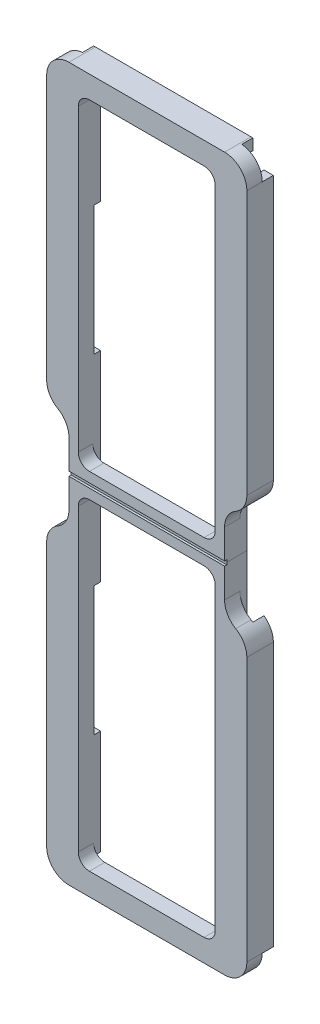
SolidWorks part; units mm, degrees
ref_plane "Front Plane" through (0, 0, 0) normal (1, 0, 0) x (0, 1, 0)
ref_plane "Top Plane" through (0, 0, 0) normal (0, 0, 1) x (0, 1, 0)
ref_plane "Right Plane" through (0, 0, 0) normal (0, 1, 0) x (-1, 0, 0)
sketch "Sketch1" plane through (0, 0, 0) normal (0, 0, 1) x (0, 1, 0)
  line L0 (279.1891, 2.675) -> (279.1891, 6.875) construction
  line L1 (-20.8109, 6.875) -> (279.1891, 6.875)
  line L2 (-20.8109, 6.875) -> (-20.8109, 2.675)
  line L3 (-20.8109, 2.675) -> (279.1891, 2.675)
  line L4 (279.1891, 6.875) -> (279.1891, 2.675)
  line L7 (129.1891, 2.675) -> (-20.8109, 2.675) construction
  line L8 (129.1891, 6.875) -> (-20.8109, 6.875) construction
  line L11 (26.1891, 2.675) -> (84.1891, 2.675)
  line L12 (26.1891, 2.675) -> (26.1891, 6.875)
  line L13 (26.1891, 6.875) -> (84.1891, 6.875)
  line L14 (84.1891, 2.675) -> (84.1891, 6.875)
  line L15 (174.1891, 2.675) -> (232.1891, 2.675)
  line L16 (174.1891, 2.675) -> (174.1891, 6.875)
  line L17 (174.1891, 6.875) -> (232.1891, 6.875)
  line L18 (232.1891, 2.675) -> (232.1891, 6.875)
  circle A0 centre (182.1891, 4.875) radius 1.65 construction
  circle A1 centre (224.1891, 4.875) radius 1.65 construction
  circle A2 centre (76.1891, 4.875) radius 1.65 construction
  circle A3 centre (34.1891, 4.875) radius 1.65 construction
  dimension "D1" = 0
  dimension "D2" = 0
  dimension "D3" = 0
  dimension "D4" = 8
  dimension "D5" = 8
  dimension "D6" = 8
  dimension "D7" = 8
extrude "Boss-Extrude1" add sketch "Sketch1" along normal blind 5 contours L2 L1 L4 L3
sketch "Sketch3" plane through (0, 0, 5) normal (0, 0, 1) x (1, 0, 0)
  line L4 (-2.675, 26.1891) -> (-2.675, 84.1891)
  line L5 (-2.675, 84.1891) -> (-6.875, 84.1891)
  line L6 (-6.875, 84.1891) -> (-6.875, 26.1891)
  line L7 (-6.875, 26.1891) -> (-2.675, 26.1891)
  line L8 (-2.675, 26.1891) -> (-2.675, 84.1891)
  line L9 (-2.675, 84.1891) -> (-6.875, 84.1891)
  line L10 (-6.875, 84.1891) -> (-6.875, 26.1891)
  line L11 (-6.875, 26.1891) -> (-2.675, 26.1891)
  line L12 (-6.875, 279.1891) -> (-6.875, -20.8109)
  line L13 (-2.675, 279.1891) -> (-6.875, 279.1891)
  line L14 (-2.675, -20.8109) -> (-2.675, 279.1891)
  line L15 (-6.875, -20.8109) -> (-2.675, -20.8109)
  line L16 (-6.875, 279.1891) -> (-6.875, -20.8109)
  line L17 (-2.675, 279.1891) -> (-6.875, 279.1891)
  line L18 (-2.675, -20.8109) -> (-2.675, 279.1891)
  line L19 (-6.875, -20.8109) -> (-2.675, -20.8109)
  line L20 (-2.675, 174.1891) -> (-2.675, 232.1891)
  line L21 (-6.875, 174.1891) -> (-2.675, 174.1891)
  line L22 (-6.875, 232.1891) -> (-6.875, 174.1891)
  line L23 (-2.675, 232.1891) -> (-6.875, 232.1891)
  line L24 (-2.675, 174.1891) -> (-2.675, 232.1891)
  line L25 (-6.875, 174.1891) -> (-2.675, 174.1891)
  line L26 (-6.875, 232.1891) -> (-6.875, 174.1891)
  line L27 (-2.675, 232.1891) -> (-6.875, 232.1891)
  dimension "D1" = 0
  dimension "D2" = 0
  dimension "D3" = 0
extrude "Cut-Extrude1" cut sketch "Sketch3" against normal through all contours L8 L9 L10 L11
sketch "Sketch4" plane through (0, 84.1891, 0) normal (0, -1, 0) x (1, 0, 0)
  line L0 (-5.175, 2.93) -> (-3.575, 2.93) construction
  line L1 (-5.175, 2.93) -> (-3.575, 2.93)
  line L2 (-2.675, 0) -> (-2.675, 5) construction
  line L3 (-2.675, 2.93) -> (-6.875, 2.93)
  line L4 (-2.675, 2.93) -> (-2.675, 5)
  line L5 (-2.675, 5) -> (-6.875, 5)
  line L6 (-6.875, 2.93) -> (-6.875, 5)
  line L7 (-4.225, 3) -> (-5.525, 3) construction
  line L8 (-4.225, 3) -> (-5.525, 3)
  line L10 (-5.925, 2.93) -> (-3.825, 2.93)
  line L11 (-5.925, 2.93) -> (-5.925, 3.5)
  line L12 (-5.925, 3.5) -> (-3.825, 3.5)
  line L13 (-3.825, 2.93) -> (-3.825, 3.5)
  line L14 (-6.875, 5) -> (-5.925, 5)
  line L15 (-6.875, 5) -> (-6.875, 2.93)
  line L16 (-6.875, 2.93) -> (-5.925, 2.93)
  line L17 (-5.925, 5) -> (-5.925, 2.93)
  line L18 (-5.925, 3.5) -> (-2.675, 3.5)
  line L19 (-5.925, 3.5) -> (-5.925, 5)
  line L20 (-5.925, 5) -> (-2.675, 5)
  line L21 (-2.675, 3.5) -> (-2.675, 5)
  line L22 (-2.675, 2.93) -> (-3.825, 2.93)
  line L23 (-2.675, 2.93) -> (-2.675, 5)
  line L24 (-2.675, 5) -> (-3.825, 5)
  line L25 (-3.825, 2.93) -> (-3.825, 5)
  dimension "D1" = 0.4
  dimension "D2" = 0.4
  dimension "D3" = 0.5
extrude "Boss-Extrude2" add sketch "Sketch4" along normal up to surface (58 mm away) contours L23 L22 L25 L24 | L19 L18 L21 L20 | L15 L14 L17 L16 up to face at (-4.775, 26.1891, 2.5)
ref_plane "Plane2" through (0, 129.1891, 0) normal (0, 1, 0) x (1, 0, 0)
split "Split1" trim tools "Plane2" bodies to split 104 resulting bodies 105
sketch "Sketch5" plane through (0, -20.8109, 0) normal (0, -1, 0) x (1, 0, 0)
  line L0 (-7.675, 3) -> (63.825, 3) construction
  line L1 (-7.675, 3) -> (63.825, 3)
  line L2 (-2.675, 5) -> (-2.675, 0) construction
  line L3 (-6.875, 5) -> (-2.675, 5)
  line L4 (-6.875, 5) -> (-6.875, 3.1)
  line L5 (-6.875, 3.1) -> (-2.675, 3.1)
  line L6 (-2.675, 5) -> (-2.675, 3.1)
  dimension "D1" = 0.1
extrude "Boss-Extrude3" add sketch "Sketch5" along normal blind 5 contours L4 L3 L6 L5
mirror "Mirror1" about plane through (0, 129.1891, 0) normal (0, 1, 0) of bodies 109 105
ref_plane "Plane3" through (28.075, 0, 0) normal (-1, 0, 0) x (0, 0, 1)
mirror "Mirror4" about plane through (28.075, 0, 0) normal (-1, 0, 0) of bodies 107
sketch "Sketch6" plane through (-2.675, 0, 0) normal (1, 0, 0) x (0, 1, 0)
  line L1 (-20.8109, 3.1) -> (-25.8109, 3.1)
  line L2 (-20.8109, 3.1) -> (-20.8109, 5)
  line L3 (-20.8109, 5) -> (-25.8109, 5)
  line L4 (-25.8109, 3.1) -> (-25.8109, 5)
extrude "Boss-Extrude4" add sketch "Sketch6" along normal blind 63
sketch "Sketch7" plane through (-2.675, 0, 0) normal (1, 0, 0) x (0, 1, 0)
  line L1 (279.1891, 3.1) -> (284.1891, 3.1)
  line L2 (279.1891, 3.1) -> (279.1891, 5)
  line L3 (279.1891, 5) -> (284.1891, 5)
  line L4 (284.1891, 3.1) -> (284.1891, 5)
extrude "Boss-Extrude5" add sketch "Sketch7" along normal blind 63
sketch "Sketch8" plane through (-2.675, 0, 0) normal (1, 0, 0) x (0, 1, 0)
  line L0 (129.1891, 3) -> (129.1891, -2) construction
  line L1 (129.1891, 3) -> (129.1891, -2)
  line L2 (-20.8109, 5) -> (279.1891, 5) construction
  line L3 (126.6891, 3.5) -> (131.6891, 3.5)
  line L4 (126.6891, 3.5) -> (126.6891, 5)
  line L5 (126.6891, 5) -> (131.6891, 5)
  line L6 (131.6891, 3.5) -> (131.6891, 5)
  line L7 (126.6891, 3.5) -> (131.6891, 5) construction
  line L8 (126.6891, 5) -> (131.6891, 3.5) construction
  point P2 (129.1891, 4.25)
  dimension "D1" = 1.5
  dimension "D2" = 5
  dimension "D3" = 2.5
extrude "Boss-Extrude6" add sketch "Sketch8" along normal blind 63 contours L4 L3 L6 L5
fillet "Fillet1" radius 5 8 edges at (63.025, -23.3109, 3.1) (63.025, 281.6891, 3.1) (63.025, 284.1891, 4.05) (-6.875, -23.3109, 3.1) (-6.875, -25.8109, 4.05) (-6.875, 284.1891, 4.05) (-6.875, 281.6891, 3.1) (63.025, -25.8109, 4.05)
sketch "Sketch9" plane through (0, 0, 5) normal (0, 0, 1) x (1, 0, 0)
  line L0 (63.025, -20.8109) -> (63.025, 279.1891) construction
  line L1 (-6.875, 128.1891) -> (63.025, 128.1891)
  line L2 (-6.875, 128.1891) -> (-6.875, 130.1891)
  line L3 (-6.875, 130.1891) -> (63.025, 130.1891)
  line L4 (63.025, 128.1891) -> (63.025, 130.1891)
  line L5 (-6.875, 128.1891) -> (63.025, 130.1891) construction
  line L6 (-6.875, 130.1891) -> (63.025, 128.1891) construction
  point P0 (28.075, 129.1891)
  dimension "D1" = 2
extrude "Cut-Extrude2" cut sketch "Sketch9" against normal blind 1
sketch "Sketch11" plane through (0, 0, 5) normal (0, 0, 1) x (1, 0, 0)
  line L1 (-2.675, 131.6891) -> (58.825, 131.6891)
  line L2 (-2.675, 131.6891) -> (-2.675, 279.1891)
  line L3 (-2.675, 279.1891) -> (58.825, 279.1891)
  line L4 (-6.875, 279.1891) -> (-6.875, 130.1891)
  line L6 (-6.875, 130.1891) -> (63.025, 130.1891)
  line L7 (58.025, 284.1891) -> (-1.875, 284.1891)
  line L11 (58.025, 284.1891) -> (-1.875, 284.1891)
  line L12 (58.825, 131.6891) -> (58.825, 279.1891)
  line L16 (-6.875, 130.1891) -> (63.025, 130.1891)
  line L17 (-6.875, 279.1891) -> (-6.875, 130.1891)
  line L19 (63.025, 130.1891) -> (63.025, 279.1891)
  line L20 (63.025, 130.1891) -> (63.025, 279.1891)
  arc A2 (63.025, 279.1891) -> (58.025, 284.1891) centre (58.025, 279.1891) ccw
  arc A3 (63.025, 279.1891) -> (58.025, 284.1891) centre (58.025, 279.1891) ccw
  arc A6 (-1.875, 284.1891) -> (-6.875, 279.1891) centre (-1.875, 279.1891) ccw
  arc A7 (-1.875, 284.1891) -> (-6.875, 279.1891) centre (-1.875, 279.1891) ccw
  dimension "D1" = 0
sketch "Sketch12" plane through (0, 0, 4) normal (0, 0, 1) x (1, 0, 0)
  line L1 (-6.875, 130.1891) -> (63.025, 130.1891)
  line L2 (-6.875, 130.1891) -> (-6.875, 128.1891)
  line L3 (-6.875, 128.1891) -> (63.025, 128.1891)
  line L4 (63.025, 130.1891) -> (63.025, 128.1891)
sketch "Sketch13" plane through (0, 0, 5) normal (0, 0, 1) x (1, 0, 0)
  line L1 (58.825, 126.6891) -> (-2.675, 126.6891)
  line L2 (58.825, 126.6891) -> (58.825, -20.8109)
  line L3 (58.825, -20.8109) -> (-2.675, -20.8109)
  line L4 (63.025, -20.8109) -> (63.025, 128.1891)
  line L5 (63.025, 128.1891) -> (-6.875, 128.1891)
  line L6 (-6.875, 128.1891) -> (-6.875, -20.8109)
  line L7 (-1.875, -25.8109) -> (58.025, -25.8109)
  line L8 (63.025, -20.8109) -> (63.025, 128.1891)
  line L9 (63.025, 128.1891) -> (-6.875, 128.1891)
  line L10 (-6.875, 128.1891) -> (-6.875, -20.8109)
  line L11 (-1.875, -25.8109) -> (58.025, -25.8109)
  line L12 (-2.675, 126.6891) -> (-2.675, -20.8109)
  arc A2 (-6.875, -20.8109) -> (-1.875, -25.8109) centre (-1.875, -20.8109) ccw
  arc A3 (-6.875, -20.8109) -> (-1.875, -25.8109) centre (-1.875, -20.8109) ccw
  arc A6 (58.025, -25.8109) -> (63.025, -20.8109) centre (58.025, -20.8109) ccw
  arc A7 (58.025, -25.8109) -> (63.025, -20.8109) centre (58.025, -20.8109) ccw
  dimension "D1" = 0
extrude "Boss-Extrude8" add sketch "Sketch11" along normal blind 5
extrude "Boss-Extrude9" add sketch "Sketch12" along normal blind 5
extrude "Boss-Extrude10" add sketch "Sketch13" along normal blind 5
sketch "Sketch15" plane through (63.025, 0, 0) normal (1, 0, 0) x (0, 1, 0)
  line L0 (130.1891, 9) -> (130.1891, 10) construction
  line L1 (279.1891, 3) -> (153.3543, 3) construction
  line L3 (-20.8109, 10) -> (-20.8109, 3.1) construction
  line L4 (279.1891, 10) -> (-20.8109, 10)
  line L5 (279.1891, 10) -> (279.1891, 3.1)
  line L6 (279.1891, 3.1) -> (-20.8109, 3.1)
  line L7 (-20.8109, 10) -> (-20.8109, 3.1)
  line L8 (279.1891, 3) -> (153.3543, 3)
  line L10 (128.1891, 9) -> (130.1891, 9) construction
  line L11 (128.1891, 10) -> (128.1891, 9) construction
  line L12 (130.1891, 9) -> (130.1891, 10)
  line L13 (128.1891, 9) -> (130.1891, 9)
  line L14 (128.1891, 10) -> (128.1891, 9)
  line L15 (105.024, -2) -> (105.024, 3) construction
  line L16 (128.1891, 10) -> (130.1891, 10)
  line L17 (128.1891, 10) -> (128.1891, 9)
  line L18 (128.1891, 9) -> (130.1891, 9)
  line L19 (130.1891, 10) -> (130.1891, 9)
  line L20 (105.024, -2) -> (105.024, 3)
  line L22 (105.024, 3.1) -> (153.3543, 3.1)
  line L23 (105.024, 3.1) -> (105.024, 10)
  line L24 (105.024, 10) -> (153.3543, 10)
  line L25 (153.3543, 3.1) -> (153.3543, 10)
  line L26 (153.3543, 3.1) -> (279.1891, 3.1)
  line L27 (153.3543, 3.1) -> (153.3543, 10)
  line L28 (153.3543, 10) -> (279.1891, 10)
  line L29 (279.1891, 3.1) -> (279.1891, 10)
  line L30 (-20.8109, 10) -> (105.024, 10)
  line L31 (-20.8109, 10) -> (-20.8109, 3.1)
  line L32 (-20.8109, 3.1) -> (105.024, 3.1)
  line L33 (105.024, 10) -> (105.024, 3.1)
  point P22 (130.1891, 9.3229)
  point P23 (0, 0)
  point P25 (0, 0)
  dimension "D1" = 0.1
extrude "Boss-Extrude11" add sketch "Sketch15" along normal blind 10 contours L31 L30 L33 L32 | L27 L26 L29 L28
sketch "Sketch16" plane through (-6.875, 0, 0) normal (-1, 0, 0) x (0, -1, 0)
  line L0 (-279.1891, 10) -> (-153.3543, 10) construction
  line L1 (-153.3543, 10) -> (-153.3543, 3.1) construction
  line L2 (-153.3543, 3.1) -> (-279.1891, 3.1) construction
  line L3 (-279.1891, 3.1) -> (-279.1891, 10) construction
  line L4 (20.8109, 3.1) -> (-105.024, 3.1) construction
  line L5 (-105.024, 3.1) -> (-105.024, 10) construction
  line L6 (-105.024, 10) -> (20.8109, 10) construction
  line L7 (20.8109, 10) -> (20.8109, 3.1) construction
  line L8 (-279.1891, 10) -> (-153.3543, 10)
  line L9 (-153.3543, 10) -> (-153.3543, 3.1)
  line L10 (-153.3543, 3.1) -> (-279.1891, 3.1)
  line L11 (-279.1891, 3.1) -> (-279.1891, 10)
  line L12 (20.8109, 3.1) -> (-105.024, 3.1)
  line L13 (-105.024, 3.1) -> (-105.024, 10)
  line L14 (-105.024, 10) -> (20.8109, 10)
  line L15 (20.8109, 10) -> (20.8109, 3.1)
extrude "Boss-Extrude12" add sketch "Sketch16" along normal blind 10
sketch "Sketch17" plane through (0, 279.1891, 0) normal (0, 1, 0) x (-1, 0, 0)
  line L1 (6.875, 3.1) -> (16.875, 3.1)
  line L2 (6.875, 3.1) -> (6.875, 10)
  line L3 (6.875, 10) -> (16.875, 10)
  line L4 (16.875, 3.1) -> (16.875, 10)
  line L5 (-63.025, 10) -> (-73.025, 10)
  line L6 (-63.025, 10) -> (-63.025, 3.1)
  line L7 (-63.025, 3.1) -> (-73.025, 3.1)
  line L8 (-73.025, 10) -> (-73.025, 3.1)
extrude "Boss-Extrude13" add sketch "Sketch17" along normal up to surface (5 mm away)
sketch "Sketch18" plane through (-6.875, 0, 0) normal (1, 0, 0) x (0, 1, 0)
  line L0 (284.1891, 3.1) -> (279.1891, 3.1) construction
  line L1 (279.7188, 3.1) -> (284.1891, 3.1)
  line L2 (279.7188, 3.1) -> (279.7188, 10)
  line L3 (279.7188, 10) -> (284.1891, 10)
  line L4 (284.1891, 3.1) -> (284.1891, 10)
extrude "Boss-Extrude14" add sketch "Sketch18" along normal up to surface (69.9 mm away) up to face at (63.025, 281.6891, 6.55)
sketch "Sketch19" plane through (0, -20.8109, 0) normal (0, -1, 0) x (1, 0, 0)
  line L1 (63.025, 3.1) -> (73.025, 3.1)
  line L2 (63.025, 3.1) -> (63.025, 10)
  line L3 (63.025, 10) -> (73.025, 10)
  line L4 (73.025, 3.1) -> (73.025, 10)
extrude "Boss-Extrude15" add sketch "Sketch19" along a picked direction on the side of the normal up to surface (5 mm away) contours L2 L1 L4 L3
sketch "Sketch20" plane through (63.025, 0, 0) normal (-1, 0, 0) x (0, -1, 0)
  line L1 (20.8109, 10) -> (25.8109, 10)
  line L2 (20.8109, 10) -> (20.8109, 3.1)
  line L3 (20.8109, 3.1) -> (25.8109, 3.1)
  line L4 (25.8109, 10) -> (25.8109, 3.1)
extrude "Boss-Extrude16" add sketch "Sketch20" along normal up to surface (79.9 mm away) up to face at (-16.875, 42.1066, 6.55)
sketch "Sketch21" plane through (0, -25.8109, 0) normal (0, -1, 0) x (1, 0, 0)
  line L1 (-16.875, 10) -> (73.025, 10)
  line L2 (-16.875, 10) -> (-16.875, 3.1)
  line L3 (-16.875, 3.1) -> (73.025, 3.1)
  line L4 (73.025, 10) -> (73.025, 3.1)
extrude "Boss-Extrude17" add sketch "Sketch21" along normal blind 5
sketch "Sketch22" plane through (0, 284.1891, 0) normal (0, 1, 0) x (-1, 0, 0)
  line L1 (-73.025, 10) -> (16.875, 10)
  line L2 (-73.025, 10) -> (-73.025, 3.1)
  line L3 (-73.025, 3.1) -> (16.875, 3.1)
  line L4 (16.875, 10) -> (16.875, 3.1)
extrude "Boss-Extrude18" add sketch "Sketch22" along normal blind 5
sketch "Sketch23" plane through (0, 0, 3.1) normal (0, 0, -1) x (1, 0, 0)
  line L0 (-16.875, -289.1891) -> (-16.875, -153.3543) construction
  line L1 (-12.675, -153.3543) -> (-16.875, -153.3543)
  line L2 (-12.675, -153.3543) -> (-12.675, -279.1891)
  line L3 (-12.675, -279.1891) -> (-16.875, -279.1891)
  line L4 (-16.875, -153.3543) -> (-16.875, -279.1891)
  line L5 (73.025, -289.1891) -> (-16.875, -289.1891) construction
  line L6 (-7.675, -284.1891) -> (63.825, -284.1891)
  line L7 (-7.675, -284.1891) -> (-7.675, -289.1891)
  line L8 (-7.675, -289.1891) -> (63.825, -289.1891)
  line L9 (63.825, -284.1891) -> (63.825, -289.1891)
  line L10 (74.825, -142.3998) -> (74.825, -129.1891)
  line L11 (74.825, -129.1891) -> (58.825, -129.1891)
  line L12 (58.825, -129.1891) -> (58.825, -279.1891)
  line L13 (58.825, -279.1891) -> (-2.675, -279.1891)
  line L14 (-2.675, -279.1891) -> (-2.675, -129.1891)
  line L15 (-2.675, -129.1891) -> (-18.675, -129.1891)
  line L16 (-18.675, -129.1891) -> (-18.675, -142.3998)
  line L17 (-12.675, -153.3543) -> (-12.675, -279.1891)
  line L18 (-7.675, -284.1891) -> (63.825, -284.1891)
  line L19 (68.825, -279.1891) -> (68.825, -153.3543)
  line L20 (74.825, -142.3998) -> (74.825, -129.1891)
  line L21 (74.825, -129.1891) -> (58.825, -129.1891)
  line L22 (58.825, -129.1891) -> (58.825, -279.1891)
  line L23 (58.825, -279.1891) -> (-2.675, -279.1891)
  line L24 (-2.675, -279.1891) -> (-2.675, -129.1891)
  line L25 (-2.675, -129.1891) -> (-18.675, -129.1891)
  line L26 (-18.675, -129.1891) -> (-18.675, -142.3998)
  line L27 (-12.675, -153.3543) -> (-12.675, -279.1891)
  line L28 (-7.675, -284.1891) -> (63.825, -284.1891)
  line L29 (68.825, -279.1891) -> (68.825, -153.3543)
  line L31 (68.825, -279.1891) -> (73.025, -279.1891)
  line L32 (68.825, -279.1891) -> (68.825, -153.3543)
  line L33 (68.825, -153.3543) -> (73.025, -153.3543)
  line L34 (73.025, -279.1891) -> (73.025, -153.3543)
  arc A6 (73.4404, -144.9278) -> (68.825, -153.3543) centre (78.825, -153.3543) ccw
  arc A7 (73.4404, -144.9278) -> (74.825, -142.3998) centre (71.825, -142.3998) ccw
  arc A8 (-18.675, -142.3998) -> (-17.2904, -144.9278) centre (-15.675, -142.3998) ccw
  arc A9 (-12.675, -153.3543) -> (-17.2904, -144.9278) centre (-22.675, -153.3543) ccw
  arc A10 (-12.675, -279.1891) -> (-7.675, -284.1891) centre (-7.675, -279.1891) ccw
  arc A11 (63.825, -284.1891) -> (68.825, -279.1891) centre (63.825, -279.1891) ccw
  arc A12 (73.4404, -144.9278) -> (68.825, -153.3543) centre (78.825, -153.3543) ccw
  arc A13 (73.4404, -144.9278) -> (74.825, -142.3998) centre (71.825, -142.3998) ccw
  arc A14 (-18.675, -142.3998) -> (-17.2904, -144.9278) centre (-15.675, -142.3998) ccw
  arc A15 (-12.675, -153.3543) -> (-17.2904, -144.9278) centre (-22.675, -153.3543) ccw
  arc A16 (-12.675, -279.1891) -> (-7.675, -284.1891) centre (-7.675, -279.1891) ccw
  arc A17 (63.825, -284.1891) -> (68.825, -279.1891) centre (63.825, -279.1891) ccw
  dimension "D1" = 0
extrude "Boss-Extrude19" add sketch "Sketch23" along normal blind 5 contours L2 L1 L4 L3 | L7 L6 L9 L8 | L32 L31 L34 L33
sketch "Sketch24" plane through (0, 0, 3.1) normal (0, 0, -1) x (1, 0, 0)
  line L0 (73.025, 30.8109) -> (73.025, -105.024) construction
  line L1 (-12.675, 20.8109) -> (-16.875, 20.8109)
  line L2 (-12.675, 20.8109) -> (-12.675, -105.024)
  line L3 (-12.675, -105.024) -> (-16.875, -105.024)
  line L4 (-16.875, 20.8109) -> (-16.875, -105.024)
  line L5 (68.825, -105.024) -> (73.025, -105.024)
  line L6 (68.825, -105.024) -> (68.825, 20.8109)
  line L7 (68.825, 20.8109) -> (73.025, 20.8109)
  line L8 (73.025, -105.024) -> (73.025, 20.8109)
  line L9 (-16.875, 30.8109) -> (73.025, 30.8109) construction
  line L10 (63.825, 25.8109) -> (-7.675, 25.8109)
  line L11 (-12.675, 20.8109) -> (-12.675, -105.024)
  line L12 (-18.675, -115.9784) -> (-18.675, -129.1891)
  line L13 (-18.675, -129.1891) -> (-2.675, -129.1891)
  line L14 (-2.675, -129.1891) -> (-2.675, 20.8109)
  line L15 (-2.675, 20.8109) -> (58.825, 20.8109)
  line L16 (58.825, 20.8109) -> (58.825, -129.1891)
  line L17 (58.825, -129.1891) -> (74.825, -129.1891)
  line L18 (74.825, -129.1891) -> (74.825, -115.9784)
  line L19 (68.825, -105.024) -> (68.825, 20.8109)
  line L20 (63.825, 25.8109) -> (-7.675, 25.8109)
  line L21 (-12.675, 20.8109) -> (-12.675, -105.024)
  line L22 (-18.675, -115.9784) -> (-18.675, -129.1891)
  line L23 (-18.675, -129.1891) -> (-2.675, -129.1891)
  line L24 (-2.675, -129.1891) -> (-2.675, 20.8109)
  line L25 (-2.675, 20.8109) -> (58.825, 20.8109)
  line L26 (58.825, 20.8109) -> (58.825, -129.1891)
  line L27 (58.825, -129.1891) -> (74.825, -129.1891)
  line L28 (74.825, -129.1891) -> (74.825, -115.9784)
  line L29 (68.825, -105.024) -> (68.825, 20.8109)
  line L30 (63.825, 25.8109) -> (-7.675, 25.8109)
  line L31 (63.825, 25.8109) -> (63.825, 30.8109)
  line L32 (63.825, 30.8109) -> (-7.675, 30.8109)
  line L33 (-7.675, 25.8109) -> (-7.675, 30.8109)
  arc A6 (-7.675, 25.8109) -> (-12.675, 20.8109) centre (-7.675, 20.8109) ccw
  arc A7 (-17.2904, -113.4505) -> (-12.675, -105.024) centre (-22.675, -105.024) ccw
  arc A8 (-17.2904, -113.4505) -> (-18.675, -115.9784) centre (-15.675, -115.9784) ccw
  arc A9 (74.825, -115.9784) -> (73.4404, -113.4505) centre (71.825, -115.9784) ccw
  arc A10 (68.825, -105.024) -> (73.4404, -113.4505) centre (78.825, -105.024) ccw
  arc A11 (68.825, 20.8109) -> (63.825, 25.8109) centre (63.825, 20.8109) ccw
  arc A12 (-7.675, 25.8109) -> (-12.675, 20.8109) centre (-7.675, 20.8109) ccw
  arc A13 (-17.2904, -113.4505) -> (-12.675, -105.024) centre (-22.675, -105.024) ccw
  arc A14 (-17.2904, -113.4505) -> (-18.675, -115.9784) centre (-15.675, -115.9784) ccw
  arc A15 (74.825, -115.9784) -> (73.4404, -113.4505) centre (71.825, -115.9784) ccw
  arc A16 (68.825, -105.024) -> (73.4404, -113.4505) centre (78.825, -105.024) ccw
  arc A17 (68.825, 20.8109) -> (63.825, 25.8109) centre (63.825, 20.8109) ccw
  dimension "D1" = 0
extrude "Boss-Extrude20" add sketch "Sketch24" along normal blind 5 contours L31 L30 L33 L32 | L2 L1 L4 L3 | L6 L5 L8 L7
fillet "Fillet2" radius 10 4 edges at (-16.875, 289.1891, 6.55) (73.025, 289.1891, 6.55) (-16.875, -30.8109, 6.55) (73.025, -30.8109, 6.55)
fillet "Fillet3" radius 10 20 edges at (68.025, 105.024, 10) (63.025, 105.024, 6.55) (68.025, 153.3543, 10) (63.025, 153.3543, 6.55) (-6.875, 153.3543, 6.55) (-11.875, 153.3543, 10) (-6.875, 105.024, 6.55) (-11.875, 105.024, 10) (-9.775, 153.3543, 3.1) (65.925, 153.3543, 3.1) (-12.675, 153.3543, 0.6) (-14.775, 153.3543, -1.9) (70.925, 153.3543, -1.9) (68.825, 153.3543, 0.6) (-9.775, 105.024, 3.1) (65.925, 105.024, 3.1) (-14.775, 105.024, -1.9) (-12.675, 105.024, 0.6) (68.825, 105.024, 0.6) (70.925, 105.024, -1.9)
fillet "Fillet4" radius 10 8 edges at (73.025, 105.024, 4.05) (68.825, 105.9488, 0.6) (73.025, 153.3543, 4.05) (68.825, 152.4295, 0.6) (-12.675, 105.9488, 0.6) (-16.875, 105.024, 4.05) (-16.875, 153.3543, 4.05) (-12.675, 152.4295, 0.6)
sketch "Sketch25" plane through (0, 126.6891, 0) normal (0, -1, 0) x (1, 0, 0)
  line L1 (-2.675, 3.5) -> (58.825, 3.5)
  line L2 (-2.675, 3.5) -> (-2.675, 10)
  line L3 (-2.675, 10) -> (58.825, 10)
  line L4 (58.825, 3.5) -> (58.825, 10)
extrude "Boss-Extrude21" add sketch "Sketch25" along normal blind 3
sketch "Sketch26" plane through (0, 131.6891, 0) normal (0, 1, 0) x (-1, 0, 0)
  line L1 (-58.825, 10) -> (2.675, 10)
  line L2 (-58.825, 10) -> (-58.825, 3.5)
  line L3 (-58.825, 3.5) -> (2.675, 3.5)
  line L4 (2.675, 10) -> (2.675, 3.5)
extrude "Boss-Extrude22" add sketch "Sketch26" along normal blind 3
fillet "Fillet5" radius 5 8 edges at (58.825, -20.8109, 6.55) (-2.675, -20.8109, 6.55) (-2.675, 123.6891, 6.75) (58.825, 279.1891, 6.55) (-2.675, 279.1891, 6.55) (-2.675, 134.6891, 6.75) (58.825, 134.6891, 6.75) (58.825, 123.6891, 6.75)
ref_plane "Plane4" through (0, 129.1891, 0) normal (0, -1, 0) x (-1, 0, 0)
split "Split2" trim tools "Plane4" bodies to split 135 resulting bodies 136 137
